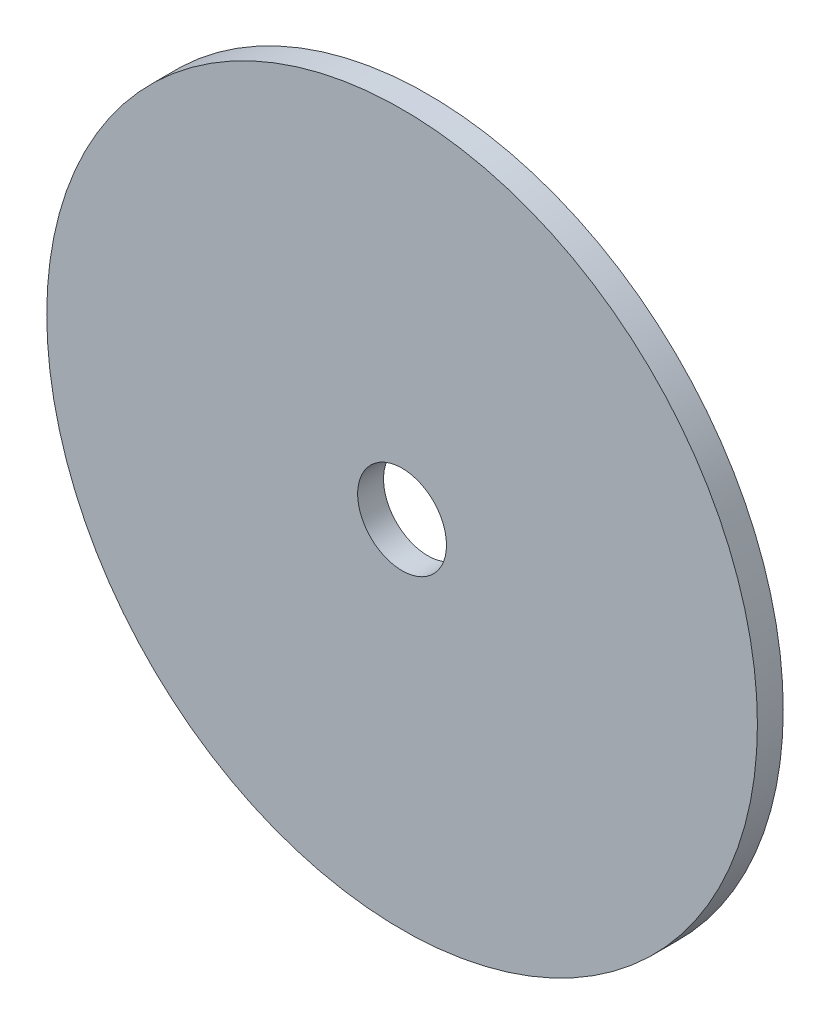
SolidWorks part; units mm, degrees
ref_plane "Plan de face" through (0, 0, 0) normal (0, 0, 1) x (1, 0, 0)
ref_plane "Plan de dessus" through (0, 0, 0) normal (0, 1, 0) x (1, 0, 0)
ref_plane "Plan de droite" through (0, 0, 0) normal (1, 0, 0) x (0, 0, -1)
sketch "Esquisse1" plane through (0, 0, 0) normal (0, 0, 1) x (1, 0, 0)
  circle A0 centre (0, 0) radius 7.5
  circle A1 centre (0, 0) radius 58
  circle A2 centre (0, 0) radius 60
  circle A3 centre (0, 0) radius 23
  circle A5 centre (0, 0) radius 25
  dimension "D1" = 120
  dimension "D2" = 116
  dimension "D3" = 15
  dimension "D4" = 50
  dimension "D5" = 46
extrude "Boss.-Extru.1" add sketch "Esquisse1" along normal blind 1.2 and the other way blind 3.1623 contours A1 A5 | A2 A1 | A5 A3 | A3 A0 region at (-56.3595, 0, 0) region at (-58.3029, 0, 0) region at (-22.3495, 0, 0) region at (-24.2929, 0, 0)
